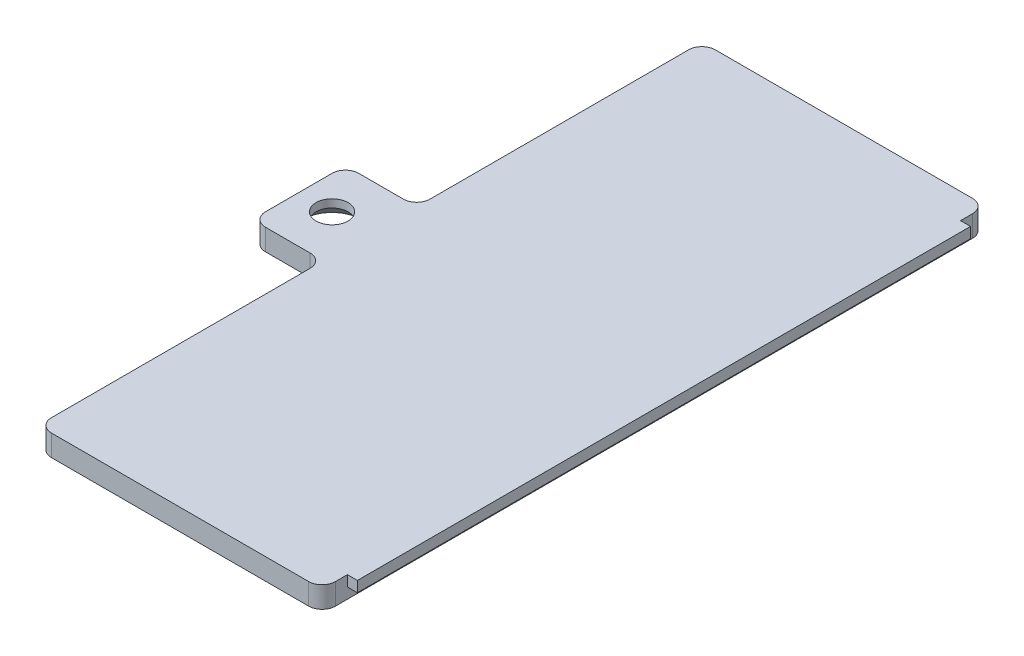
SolidWorks part; units mm, degrees
ref_plane "Front Plane" through (0, 0, 0) normal (0, 0, 1) x (1, 0, 0)
ref_plane "Top Plane" through (0, 0, 0) normal (0, 1, 0) x (1, 0, 0)
ref_plane "Right Plane" through (0, 0, 0) normal (1, 0, 0) x (0, 0, -1)
sketch "Door Plate 1.6 + centred screw tab Sketch" plane through (0, 0, 0) normal (0, 1, 0) x (1, 0, 0)
  line L0 (9.35, 15.1) -> (30.65, 15.1)
  line L1 (30.65, 15.1) -> (30.65, 64.9)
  line L2 (30.65, 64.9) -> (9.35, 64.9)
  line L3 (9.35, 64.9) -> (9.35, 43.5)
  line L4 (9.35, 43.5) -> (4, 43.5)
  line L5 (4, 43.5) -> (4, 36.5)
  line L6 (4, 36.5) -> (9.35, 36.5)
  line L7 (9.35, 36.5) -> (9.35, 15.1)
extrude "Door Plate 1.6 + centred screw tab" add sketch "Door Plate 1.6 + centred screw tab Sketch" along normal blind 1.6
ref_plane "Hook Tongue Plane d17" through (0, 0, -17) normal (0, 0, 1) x (1, 0, 0)
sketch "Screw Hole 2.4 (free) Sketch" plane through (0, 0, 0) normal (0, 1, 0) x (1, 0, 0)
  circle A0 centre (6.5, 40) radius 1.2
extrude "Screw Hole 2.4 (free)" cut sketch "Screw Hole 2.4 (free) Sketch" along normal through all
chamfer "Screw CSK 90deg (M2)" distance 1 angle 45 1 edges at (6.5, 0, -38.8)
ref_plane "Hook Flange Plane y0.8" through (0, 0.8, 0) normal (0, 1, 0) x (1, 0, 0)
sketch "Hook Flange 0.75 x 0.8 (inner-face plane) Sketch" plane through (0, 0.8, 0) normal (0, 1, 0) x (1, 0, 0)
  line L0 (30.5, 17) -> (31.4, 17)
  line L1 (31.4, 17) -> (31.4, 63)
  line L2 (31.4, 63) -> (30.5, 63)
  line L3 (30.5, 63) -> (30.5, 17)
extrude "Hook Flange 0.75 x 0.8 (inner-face plane)" add sketch "Hook Flange 0.75 x 0.8 (inner-face plane) Sketch" along normal blind 0.8
fillet "Door Corners R1 (print)" radius 1 8 edges at (9.35, 0.8, -36.5) (4, 0.8, -36.5) (4, 0.8, -43.5) (9.35, 0.8, -43.5) (9.35, 0.8, -64.9) (30.65, 0.8, -64.9) (30.65, 0.8, -15.1) (9.35, 0.8, -15.1)
